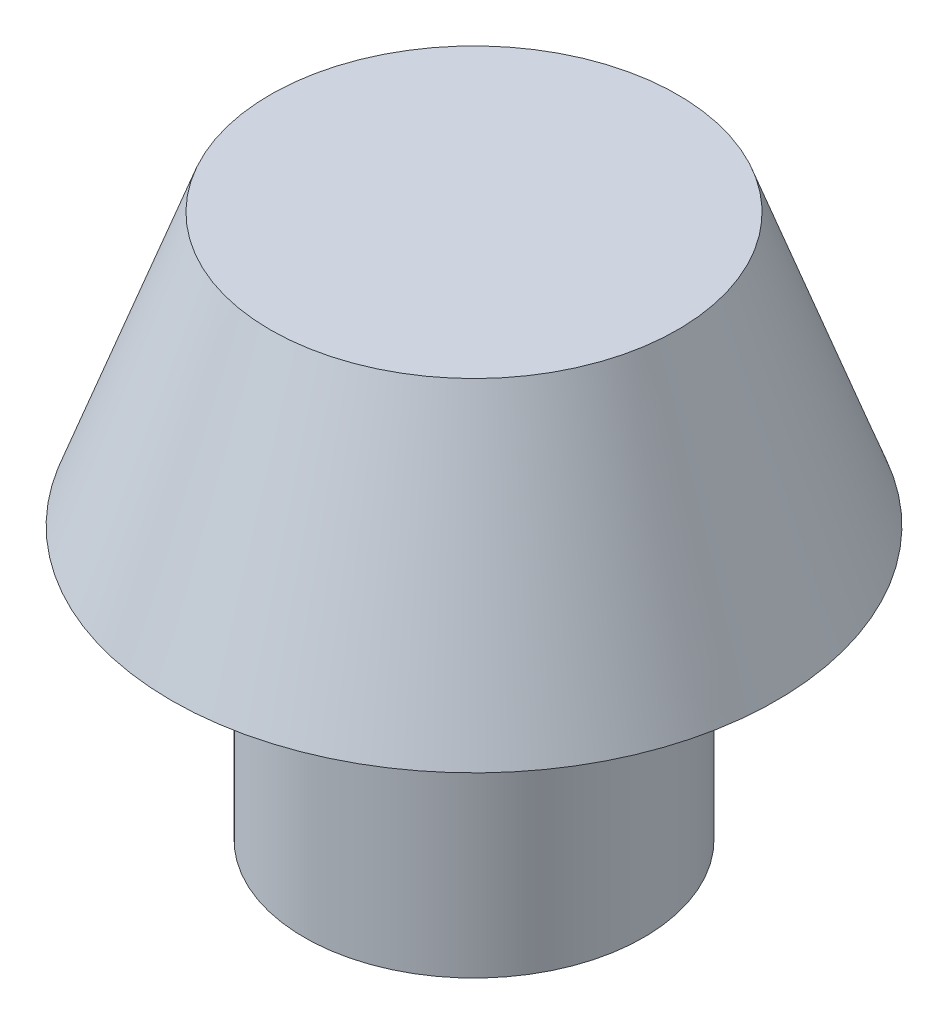
SolidWorks part; units mm, degrees
ref_plane "Front Plane" through (0, 0, 0) normal (0, 0, 1) x (1, 0, 0)
ref_plane "Top Plane" through (0, 0, 0) normal (0, 1, 0) x (1, 0, 0)
ref_plane "Right Plane" through (0, 0, 0) normal (1, 0, 0) x (0, 0, -1)
sketch "Sketch1" plane through (0, 0, 0) normal (0, 1, 0) x (1, 0, 0)
  circle A0 centre (0, 0) radius 5
  dimension "D1" = 10
extrude "Boss-Extrude1" add sketch "Sketch1" along normal blind 4
sketch "Sketch2" plane through (0, 0, 0) normal (0, -1, 0) x (1, 0, 0)
  circle A0 centre (0, 0) radius 2.5
  dimension "D1" = 5
extrude "Boss-Extrude2" add sketch "Sketch2" along normal blind 4
chamfer "Chamfer5" distance 2 angle 70 1 edges at (0, 4, 5) first distance on face at (0, 4, 5)
